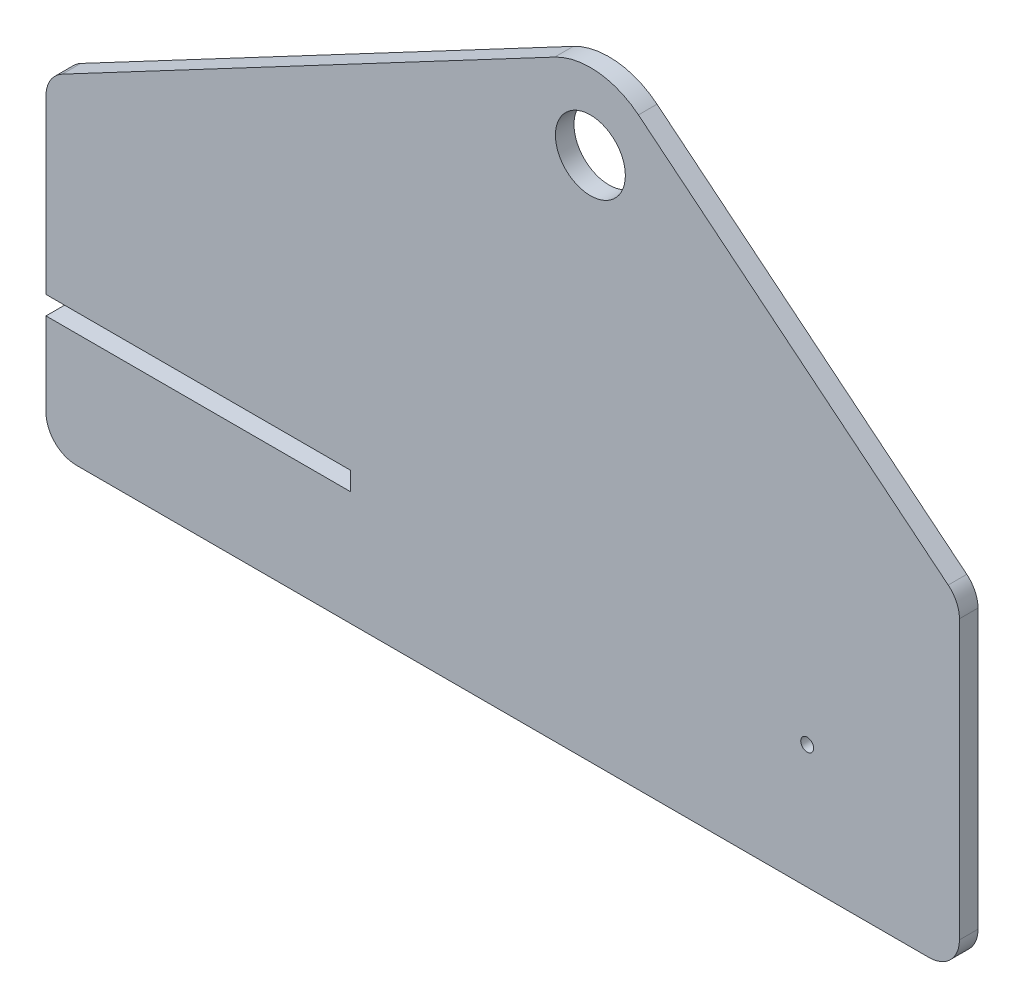
SolidWorks part; units mm, degrees
material "Corrugated Paper"
ref_plane "Front Plane" through (0, 0, 0) normal (0, 0, 1) x (1, 0, 0)
ref_plane "Top Plane" through (0, 0, 0) normal (0, 1, 0) x (1, 0, 0)
ref_plane "Right Plane" through (0, 0, 0) normal (1, 0, 0) x (0, 0, -1)
sketch "Sketch2" plane through (0, 0, 0) normal (0, 0, 1) x (1, 0, 0)
  line L0 (-50.8, 1.5494) -> (-50.8, 7.8994)
  line L1 (-50.8, -7.8994) -> (50.8, -7.8994)
  line L2 (-50.8, -7.8994) -> (-50.8, -1.5494)
  line L3 (-50.8, 7.8994) -> (50.8, 7.8994)
  line L4 (50.8, -7.8994) -> (50.8, 7.8994)
  line L5 (-50.8, -7.8994) -> (50.8, 7.8994) construction
  line L6 (-50.8, 7.8994) -> (50.8, -7.8994) construction
  line L7 (-50.8, 1.5494) -> (0, 1.5494)
  line L9 (-50.8, -1.5494) -> (0, -1.5494)
  line L10 (0, 1.5494) -> (0, -1.5494)
  point P0 (0, 0)
  dimension "D1" = 50.8
  dimension "D3" = 3.0988
  dimension "D2" = 6.35
extrude "Boss-Extrude1" add sketch "Sketch2" along normal blind 3.0988
sketch "Sketch3" plane through (0, 0, 0) normal (0, 0, 1) x (1, 0, 0)
  line L0 (-50.8, -7.8994) -> (-50.8, -20.5994)
  line L1 (-50.8, -20.5994) -> (101.6, -20.5994)
  line L2 (101.6, -20.5994) -> (101.6, 33.2994)
  line L3 (50.8, 7.8994) -> (-50.8, 7.8994) construction
  line L5 (-50.8, 33.2994) -> (-50.8, 7.8994)
  line L6 (-50.8, -7.8994) -> (50.8, -7.8994) construction
  line L7 (50.8, -7.8994) -> (50.8, 7.8994) construction
  line L8 (-50.8, -7.8994) -> (50.8, -7.8994)
  line L9 (50.8, -7.8994) -> (50.8, 7.8994)
  line L10 (50.8, 7.8994) -> (-50.8, 7.8994)
  line L12 (48.047, 76.9142) -> (101.6, 33.2994)
  line L13 (34.0795, 78.2881) -> (-50.8, 33.2994)
  circle A0 centre (76.2, 0) radius 1.0795
  circle A1 centre (40.027, 67.0668) radius 5.8357
  arc A2 (48.047, 76.9142) -> (34.0795, 78.2881) centre (40.027, 67.0668) ccw
  point P13 (0, 0)
  dimension "D1" = 2.159
  dimension "D7" = 25.4
  dimension "D2" = 12.7
  dimension "D3" = 25.4
  dimension "D4" = 152.4
  dimension "D5" = 25.4
  dimension "D6" = 76.2
extrude "Boss-Extrude2" add sketch "Sketch3" along normal blind 3.0988
fillet "Fillet1" radius 5.08 4 edges at (101.6, 33.2994, 1.5494) (101.6, -20.5994, 1.5494) (-50.8, -20.5994, 1.5494) (-50.8, 33.2994, 1.5494)
equation "\"rodThick\"= 0.085in"
equation "\"thick\"= 0.122in"
equation "\"clear\"= 0.003in"
equation "\"D3@Sketch2\"=\"thick\""
equation "\"D1@Boss-Extrude1\"=\"thick\""
equation "\"D1@Sketch3\"=\"rodThick\""
equation "\"D1@Boss-Extrude2\"=\"thick\""
